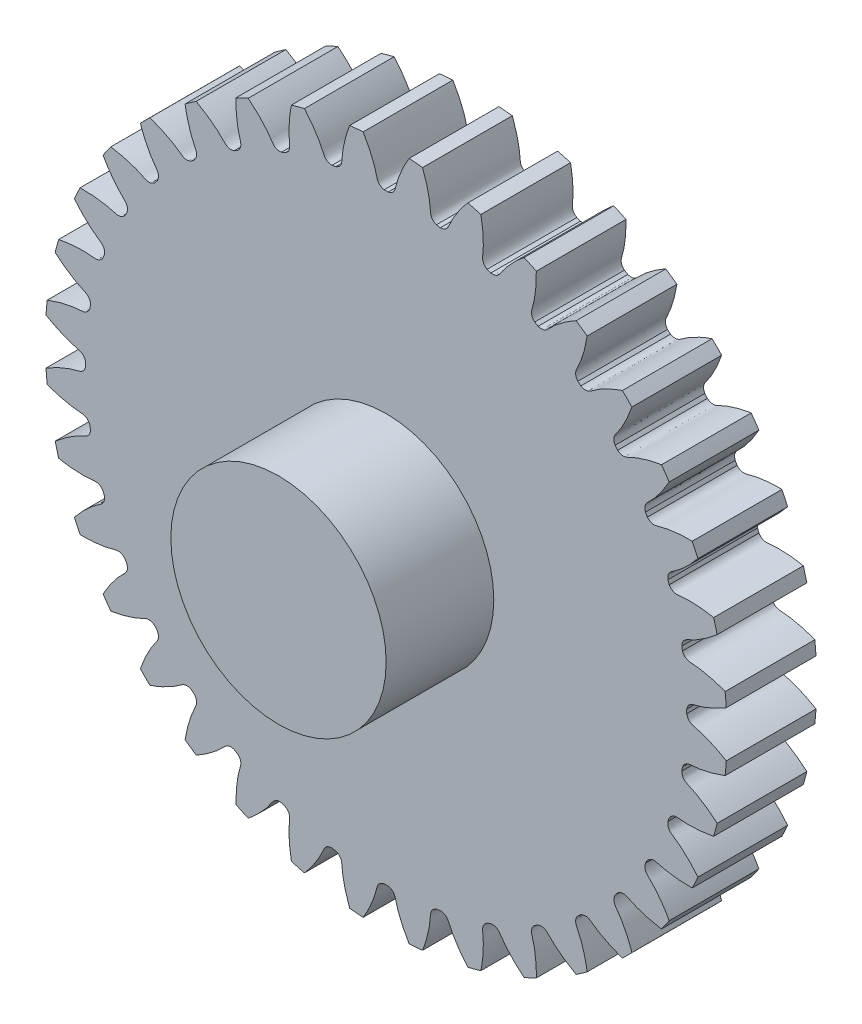
SolidWorks part; units mm, degrees
ref_plane "前视基准面" through (0, 0, 0) normal (0, 0, 1) x (1, 0, 0)
ref_plane "上视基准面" through (0, 0, 0) normal (0, 1, 0) x (1, 0, 0)
ref_plane "右视基准面" through (0, 0, 0) normal (1, 0, 0) x (0, 0, -1)
other "Configuration Table"
sketch "草图1" plane through (0, 0, 0) normal (0, 0, 1) x (1, 0, 0)
  circle A0 centre (0, 0) radius 9.5
extrude "凸台-拉伸1" add sketch "草图1" along normal blind 2.5
ref_axis "基准轴1" through (0, 0, 2.5) along (0, 0, -1)
sketch "草图2" plane through (0, 0, 0) normal (0, 0, 1) x (1, 0, 0)
  line L0 (0, 0) -> (0, 9.5) construction
  circle A0 centre (0, 0) radius 9.5 construction
  arc A1 (0.0549, 8.3748) -> (-0.0549, 8.3748) centre (0, 0) ccw
  arc A2 (1.757, 10.7884) -> (-1.757, 10.7884) centre (0, 0) ccw
  spline S0 degree 3 poles (0.0549, 8.3748) (0.235, 8.4152) (0.2505, 8.5493) (0.2882, 8.6914) (0.2997, 8.7319) (0.3131, 8.7753) (0.3284, 8.8217) (0.3457, 8.871) (0.3652, 8.9231) (0.3869, 8.9779) (0.4111, 9.0354) (0.4378, 9.0956) (0.4671, 9.1582) (0.4992, 9.2232) (0.5341, 9.2907) (0.5719, 9.3603) (0.6128, 9.4322) (0.6569, 9.5061) (0.7043, 9.582) (0.755, 9.6598) (0.8091, 9.7393) (0.8668, 9.8205) (0.9281, 9.9032) (0.9931, 9.9874) (1.0619, 10.0729) (1.1346, 10.1596) (1.2112, 10.2474) (1.2919, 10.3361) (1.3766, 10.4256) (1.4655, 10.5159) (1.5912, 10.6386) (1.6895, 10.7288) (1.757, 10.7884) knots 0 0 0 0 0.120371 0.133303 0.147364 0.162556 0.178878 0.19633 0.214913 0.234626 0.255469 0.277443 0.300547 0.324782 0.350146 0.376641 0.404267 0.433023 0.462909 0.493925 0.526072 0.559349 0.593757 0.629294 0.665963 0.703761 0.74269 0.782749 0.823939 0.866258 0.909709 1 1 1 1
  spline S1 degree 3 poles (-0.0549, 8.3748) (-0.235, 8.4152) (-0.2505, 8.5493) (-0.2882, 8.6914) (-0.2997, 8.7319) (-0.3131, 8.7753) (-0.3284, 8.8217) (-0.3457, 8.871) (-0.3652, 8.9231) (-0.3869, 8.9779) (-0.4111, 9.0354) (-0.4378, 9.0956) (-0.4671, 9.1582) (-0.4992, 9.2232) (-0.5341, 9.2907) (-0.5719, 9.3603) (-0.6128, 9.4322) (-0.6569, 9.5061) (-0.7043, 9.582) (-0.755, 9.6598) (-0.8091, 9.7393) (-0.8668, 9.8205) (-0.9281, 9.9032) (-0.9931, 9.9874) (-1.0619, 10.0729) (-1.1346, 10.1596) (-1.2112, 10.2474) (-1.2919, 10.3361) (-1.3766, 10.4256) (-1.4655, 10.5159) (-1.5912, 10.6386) (-1.6895, 10.7288) (-1.757, 10.7884) knots 0 0 0 0 0.120371 0.133303 0.147364 0.162556 0.178878 0.19633 0.214913 0.234626 0.255469 0.277443 0.300547 0.324782 0.350146 0.376641 0.404267 0.433023 0.462909 0.493925 0.526072 0.559349 0.593757 0.629294 0.665963 0.703761 0.74269 0.782749 0.823939 0.866258 0.909709 1 1 1 1
extrude "切除-拉伸1" cut sketch "草图2" along normal through all
pattern_circular "阵列(圆周)1" count 36 every 10 about axis through (0, 0, 2.5) along (0, 0, -1) of "切除-拉伸1"
sketch "草图3" plane through (0, 0, 0) normal (0, 0, 1) x (1, 0, 0)
  circle A0 centre (0, 0) radius 9 construction
  dimension "Dn" = 18
sketch "草图4" plane through (0, 0, 2.5) normal (0, 0, 1) x (1, 0, 0)
  circle A0 centre (0, 0) radius 3
  dimension "D1" = 6
extrude "凸台-拉伸2" add sketch "草图4" along normal blind 3
